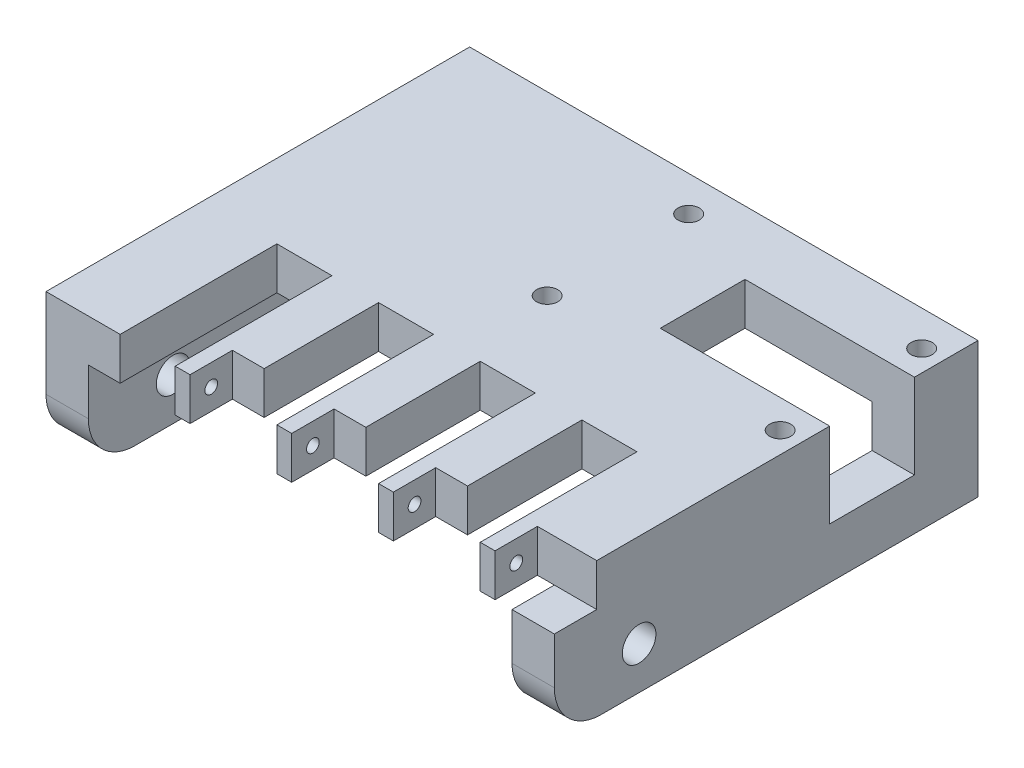
SolidWorks part; units mm, degrees
material "Plain Carbon Steel"
ref_plane "Front Plane" through (0, 0, 0) normal (0, 0, 1) x (1, 0, 0)
ref_plane "Top Plane" through (0, 0, 0) normal (0, 1, 0) x (1, 0, 0)
ref_plane "Right Plane" through (0, 0, 0) normal (1, 0, 0) x (0, 0, -1)
sketch "Sketch1" plane through (0, 0, 0) normal (0, 1, 0) x (1, 0, 0)
  line L1 (60, -50) -> (-60, -50)
  line L2 (60, -50) -> (60, 50)
  line L3 (60, 50) -> (-60, 50)
  line L4 (-60, -50) -> (-60, 50)
  line L5 (60, -50) -> (-60, 50) construction
  line L6 (60, 50) -> (-60, -50) construction
  point P0 (0, 0)
  dimension "D1" = 120
  dimension "D2" = 100
extrude "Boss-Extrude1" add sketch "Sketch1" along normal blind 10 contours L3 L1 | L3 L4 L1 | L3 L1 L2 region at (0, 0, 0)
sketch "Sketch2" plane through (0, 0, 50) normal (0, 0, 1) x (1, 0, 0)
  line L0 (-60, 0) -> (60, 0) construction
  line L1 (60, 10) -> (-60, 10) construction
  line L4 (-29.5, -10) -> (-42.5, -10)
  line L5 (-29.5, -10) -> (-29.5, 10)
  line L6 (-29.5, 10) -> (-42.5, 10)
  line L7 (-42.5, -10) -> (-42.5, 10)
  line L8 (-29.5, -10) -> (-42.5, 10) construction
  line L9 (-29.5, 10) -> (-42.5, -10) construction
  line L10 (-5.5, -10) -> (-18.5, -10)
  line L11 (-5.5, -10) -> (-5.5, 10)
  line L12 (-5.5, 10) -> (-18.5, 10)
  line L13 (-18.5, -10) -> (-18.5, 10)
  line L14 (-5.5, -10) -> (-18.5, 10) construction
  line L15 (-5.5, 10) -> (-18.5, -10) construction
  line L16 (18.5, -10) -> (5.5, -10)
  line L17 (18.5, -10) -> (18.5, 10)
  line L18 (18.5, 10) -> (5.5, 10)
  line L19 (5.5, -10) -> (5.5, 10)
  line L20 (18.5, -10) -> (5.5, 10) construction
  line L21 (18.5, 10) -> (5.5, -10) construction
  line L22 (42.5, -10) -> (29.5, -10)
  line L23 (42.5, -10) -> (42.5, 10)
  line L24 (42.5, 10) -> (29.5, 10)
  line L25 (29.5, -10) -> (29.5, 10)
  line L26 (42.5, -10) -> (29.5, 10) construction
  line L27 (42.5, 10) -> (29.5, -10) construction
  line L29 (60, 0) -> (-60, 0) construction
  point P7 (-36, 0)
  point P8 (-12, 0)
  point P9 (12, 0)
  point P10 (36, 0)
  point P11 (-36, 0)
  point P16 (-12, 0)
  point P21 (12, 0)
  point P26 (36, 0)
  point P33 (0, 0)
  dimension "D1" = 120
  dimension "D3" = 13
extrude "Cut-Extrude1" cut sketch "Sketch2" against normal blind 37
sketch "Sketch3" plane through (0, 0, 50) normal (0, 0, 1) x (1, 0, 0)
  line L0 (60, 10) -> (60, 0) construction
  line L1 (-18.5, 0) -> (-26, 0)
  line L2 (-18.5, 0) -> (-18.5, 10)
  line L3 (-18.5, 10) -> (-26, 10)
  line L4 (-26, 0) -> (-26, 10)
  line L5 (5.5, 0) -> (-2, 0)
  line L6 (5.5, 0) -> (5.5, 10)
  line L7 (5.5, 10) -> (-2, 10)
  line L8 (-2, 0) -> (-2, 10)
  line L9 (29.5, 0) -> (22, 0)
  line L10 (29.5, 0) -> (29.5, 10)
  line L11 (29.5, 10) -> (22, 10)
  line L12 (22, 0) -> (22, 10)
  line L13 (46, 0) -> (60, 0)
  line L14 (46, 0) -> (46, 10)
  line L15 (46, 10) -> (60, 10)
  line L16 (60, 0) -> (60, 10)
  line L17 (60, 0) -> (42.5, 0) construction
  line L18 (5.5, 10) -> (5.5, 0) construction
  line L19 (5.5, 0) -> (-5.5, 0) construction
  line L21 (-29.5, 0) -> (-29.5, 10) construction
  line L22 (-5.5, 0) -> (-5.5, 10) construction
  line L23 (42.5, 0) -> (42.5, 10) construction
  line L24 (18.5, 0) -> (18.5, 10) construction
  line L25 (-18.5, 0) -> (-5.5, 0) construction
  line L26 (-18.5, 10) -> (-18.5, 0) construction
  line L29 (-18.5, 10) -> (-29.5, 10) construction
  line L33 (5.5, 10) -> (-5.5, 10) construction
  line L34 (29.5, 10) -> (18.5, 10) construction
  line L35 (60, 10) -> (42.5, 10) construction
  dimension "D1" = 3.5
  dimension "D2" = 3.5
  dimension "D3" = 3.5
  dimension "D4" = 3.5
extrude "Cut-Extrude2" cut sketch "Sketch3" against normal blind 10
sketch "Sketch4" plane through (46, 0, 0) normal (1, 0, 0) x (0, 0, -1)
  line L1 (-40, 0) -> (-50, 0) construction
  line L2 (-50, 10) -> (-50, 0) construction
  circle A0 centre (-45, 5) radius 1.5
  dimension "D1" = 3
  dimension "D2" = 5
  dimension "D3" = 5
extrude "Cut-Extrude3" cut sketch "Sketch4" against normal up to surface (75.5 mm away) up to face at (-29.5, 5, 31.5)
sketch "Sketch6" plane through (60, 0, 0) normal (1, 0, 0) x (0, 0, -1)
  line L0 (50, 10) -> (50, 0) construction
  line L1 (-50, 0) -> (50, 0)
  line L2 (-50, 0) -> (-50, -11)
  line L3 (-39, -22) -> (50, -22)
  line L4 (50, 0) -> (50, -22)
  line L5 (-50, -11) -> (-50, -22) construction
  line L6 (-50, -22) -> (-39, -22) construction
  circle A0 centre (-30, -12) radius 3.9688
  arc A1 (-50, -11) -> (-39, -22) centre (-39, -11) ccw
  dimension "D2" = 7.9375
  dimension "D1" = 22
  dimension "D3" = 20
  dimension "D4" = 12
extrude "Boss-Extrude2" add sketch "Sketch6" against normal blind 10
mirror "Mirror1" about plane through (0, 0, 0) normal (1, 0, 0) of "Boss-Extrude2"
sketch "Sketch7" plane through (0, 10, 0) normal (0, 1, 0) x (1, 0, 0)
  line L0 (60, -40) -> (60, 50) construction
  line L1 (60, 35) -> (20, 35)
  line L2 (60, 35) -> (60, 15)
  line L3 (60, 15) -> (20, 15)
  line L4 (20, 35) -> (20, 15)
  line L5 (60, 50) -> (-60, 50) construction
  line L6 (-5.5, -13) -> (5.5, -13) construction
  line L7 (0, 41.7) -> (55, 41.7) construction
  line L8 (0, 41.7) -> (0, 8.3) construction
  line L9 (0, 8.3) -> (55, 8.3) construction
  line L10 (55, 41.7) -> (55, 8.3) construction
  line L11 (-5.5, -13) -> (-5.5, -50) construction
  line L12 (5.5, -13) -> (5.5, -40) construction
  circle A0 centre (55, 8.3) radius 2.5
  circle A1 centre (55, 41.7) radius 2.5
  circle A2 centre (0, 41.7) radius 2.5
  circle A3 centre (0, 8.3) radius 2.5
  point P6 (60, 25)
  point P17 (20, 25)
  point P18 (0, 25)
  point P25 (0, -13)
  dimension "D5" = 5
  dimension "25" = 25
  dimension "D2" = 20
  dimension "D3" = 40
  dimension "D4" = 5
  dimension "D6" = 33.4
extrude "Cut-Extrude4" cut sketch "Sketch7" against normal blind 20
sketch "Sketch8" plane through (0, -22, 0) normal (0, -1, 0) x (1, 0, 0)
  line L2 (50, 39) -> (60, 39) construction
  line L3 (50, -50) -> (60, -50) construction
  circle A0 centre (55, 15) radius 2.5
  point P10 (55, 39)
  dimension "D1" = 5
  dimension "D2" = 65
extrude "Cut-Extrude5" cut sketch "Sketch8" against normal blind 20
